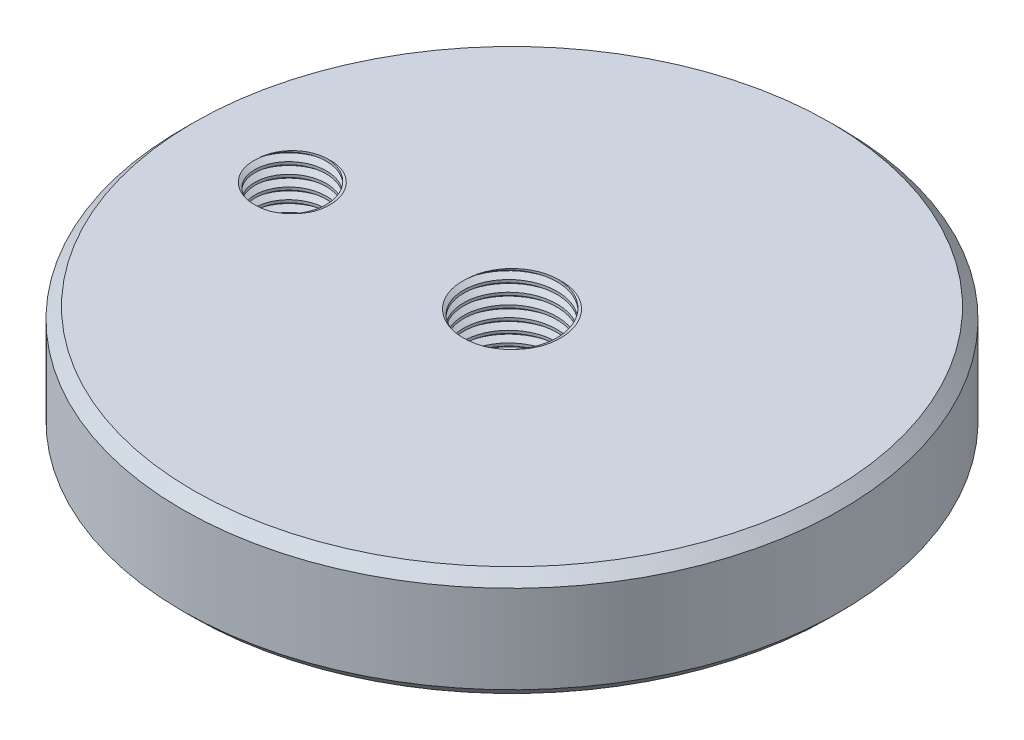
SolidWorks part; units mm, degrees
ref_plane "Front Plane" through (0, 0, 0) normal (0, 0, 1) x (1, 0, 0)
ref_plane "Top Plane" through (0, 0, 0) normal (0, 1, 0) x (1, 0, 0)
ref_plane "Right Plane" through (0, 0, 0) normal (1, 0, 0) x (0, 0, -1)
sketch "Sketch1" plane through (0, 0, 0) normal (0, 1, 0) x (1, 0, 0)
  circle A0 centre (0, 0) radius 30
  circle A1 centre (-20, 0) radius 3.25
  circle A2 centre (0, 0) radius 4.25
  dimension "D1" = 60
  dimension "D2" = 6.5
  dimension "D3" = 8.5
  dimension "D4" = 20
extrude "Boss-Extrude1" add sketch "Sketch1" along normal blind 10
thread "Thread1" pitch 1 method cut profile "Thread Profile1" start angle 0, offset 1, length 15, pitch 1, diameter 6.5
ref_plane "Plane1" through (-23.25, 11, 0) normal (0, 0, 1) x (-1, 0, 0)
sketch "Thread Profile1" plane through (-23.25, 11, 0) normal (0, 0, 1) x (-1, 0, 0)
  line L0 (0, 0) -> (0, 1) construction
  line L1 (0, 0) -> (0.5413, 0.3125)
  line L2 (0.5413, 0.3125) -> (0.5413, 0.4375)
  line L3 (0.5413, 0.4375) -> (0, 0.75)
  line L4 (0.5413, 0.375) -> (0, 0.375) construction
  line L11 (0, 0) -> (0, 0.75)
  point P2 (0, 0)
  dimension "Pitch" = 1
  dimension "Profile_Angle" = 60
  dimension "Profile_Land" = 0.125
  dimension "Profile_Height" = 0.5413
thread "Thread2" pitch 1 method cut profile "Thread Profile2" start angle 0, offset 1, length 15, pitch 1, diameter 8.5
ref_plane "Plane2" through (-4.25, 11, 0) normal (0, 0, 1) x (-1, 0, 0)
sketch "Thread Profile2" plane through (-4.25, 11, 0) normal (0, 0, 1) x (-1, 0, 0)
  line L0 (0, 0) -> (0, 1) construction
  line L1 (0, 0) -> (0.5413, 0.3125)
  line L2 (0.5413, 0.3125) -> (0.5413, 0.4375)
  line L3 (0.5413, 0.4375) -> (0, 0.75)
  line L4 (0.5413, 0.375) -> (0, 0.375) construction
  line L11 (0, 0) -> (0, 0.75)
  point P2 (0, 0)
  dimension "Pitch" = 1
  dimension "Profile_Angle" = 60
  dimension "Profile_Land" = 0.125
  dimension "Profile_Height" = 0.5413
chamfer "Chamfer1" distance 1 angle 45 2 edges at (0, 0, 30) (0, 10, 30)
